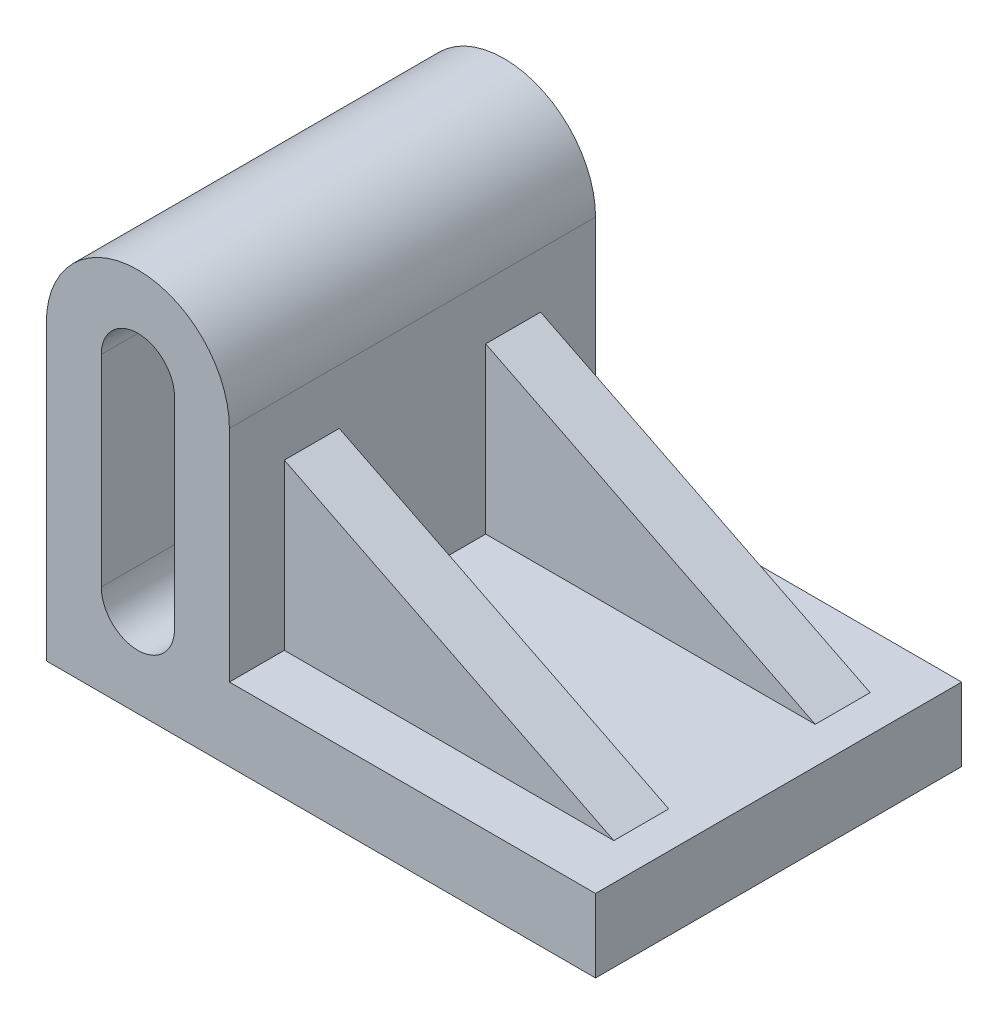
SolidWorks part; units mm, degrees
ref_plane "Front Plane" through (0, 0, 0) normal (0, 0, 1) x (1, 0, 0)
ref_plane "Top Plane" through (0, 0, 0) normal (0, 1, 0) x (1, 0, 0)
ref_plane "Right Plane" through (0, 0, 0) normal (1, 0, 0) x (0, 0, -1)
sketch "Sketch1" plane through (0, 0, 0) normal (0, 0, 1) x (1, 0, 0)
  line L0 (0, 80) -> (0, 0)
  line L1 (0, 0) -> (150, 0)
  line L2 (150, 0) -> (150, 20)
  line L3 (150, 20) -> (50, 20)
  line L4 (50, 20) -> (50, 80)
  circle A0 centre (25, 80) radius 25
  point P3 (0, 0)
  point P10 (50, 80)
  point P11 (0, 86.4659)
  point P12 (50, 80)
  point P13 (50, 80)
  point P14 (50, 80)
  point P15 (50, 80)
  point P16 (50, 80)
  point P17 (50, 80)
  dimension "D4" = 50
  dimension "D1" = 150
  dimension "D2" = 80
  dimension "D3" = 20
extrude "Boss-Extrude1" add sketch "Sketch1" against normal blind 50 and the other way blind 50 contours A0 | A0 L0 L1 L2 L3 L4 region at (25, 53.3, 0) region at (25, 80, 0)
sketch "Sketch2" plane through (0, 0, 50) normal (0, 0, 1) x (1, 0, 0)
  line L0 (25, 80) -> (25, 25) construction
  line L1 (35, 80) -> (35, 25)
  line L2 (15, 80) -> (15, 25)
  line L4 (0, 0) -> (150, 0) construction
  arc A0 (35, 80) -> (15, 80) centre (25, 80) ccw
  arc A1 (15, 25) -> (35, 25) centre (25, 25) ccw
  arc A3 (50, 80) -> (0, 80) centre (25, 80) ccw construction
  point P2 (25, 52.5)
  dimension "D3" = 10
  dimension "D1" = 55
  dimension "D2" = 25
extrude "Cut-Extrude2" cut sketch "Sketch2" against normal through all
sketch "Sketch4" plane through (0, 0, 0) normal (0, 0, 1) x (1, 0, 0)
  line L0 (50, 65) -> (50, 20)
  line L1 (50, 20) -> (50, 80) construction
  line L2 (50, 20) -> (140, 20)
  line L3 (150, 20) -> (50, 20) construction
  line L4 (140, 20) -> (50, 65)
  line L5 (150, 0) -> (150, 20) construction
  dimension "D1" = 10
  dimension "D2" = 45
extrude "Boss-Extrude2" add sketch "Sketch4" along normal blind 35 and the other way blind 35
sketch "Sketch5" plane through (0, 20, 0) normal (0, 1, 0) x (1, 0, 0)
  line L0 (50, 35) -> (50, -35) construction
  line L1 (50, 20) -> (177.2407, 20)
  line L2 (50, 20) -> (50, -20)
  line L3 (50, -20) -> (177.2407, -20)
  line L4 (177.2407, 20) -> (177.2407, -20)
  line L5 (-57.75, 0) -> (57.75, 0) construction
  dimension "D1" = 20
  dimension "D2" = 40
extrude "Cut-Extrude3" cut sketch "Sketch5" along normal through all
